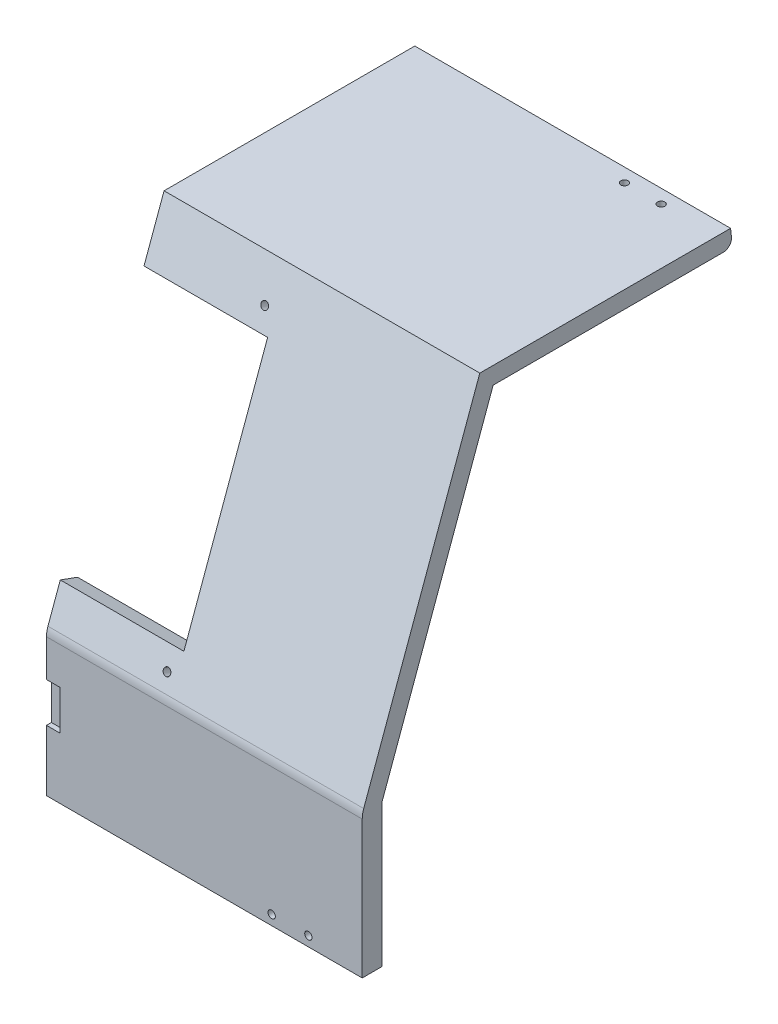
SolidWorks part; units mm, degrees
ref_plane "Front Plane" through (0, 0, 0) normal (0, 0, 1) x (1, 0, 0)
ref_plane "Top Plane" through (0, 0, 0) normal (0, 1, 0) x (1, 0, 0)
ref_plane "Right Plane" through (0, 0, 0) normal (1, 0, 0) x (0, 0, -1)
sketch "Sketch1" plane through (0, 0, 0) normal (0, 0, 1) x (1, 0, 0)
  line L0 (0, 0) -> (170, 0)
  line L1 (170, 0) -> (170, 130)
  line L2 (170, 130) -> (0, 130)
  line L3 (0, 130) -> (0, 0)
  dimension "D1" = 170
  dimension "D2" = 130
extrude "Boss-Extrude1" add sketch "Sketch1" along normal blind 8
sketch "Sketch2" plane through (0, 0, 8) normal (0, 0, 1) x (1, 0, 0)
  line L0 (85, 130) -> (85, 0) construction
  line L1 (170, 130) -> (0, 130) construction
  line L2 (0, 0) -> (170, 0) construction
  line L3 (0, 65) -> (170, 65) construction
  line L4 (0, 130) -> (0, 0) construction
  line L5 (170, 0) -> (170, 130) construction
  line L6 (6.55, 123.35) -> (163.45, 123.35) construction
  line L7 (163.45, 123.35) -> (163.45, 6.65) construction
  line L8 (163.45, 6.65) -> (6.55, 6.65) construction
  line L9 (6.55, 6.65) -> (6.55, 123.35) construction
  line L10 (2.5, 115) -> (167.5, 115)
  line L11 (2.5, 115) -> (2.5, 15)
  line L12 (2.5, 15) -> (167.5, 15)
  line L13 (167.5, 15) -> (167.5, 115)
  circle A0 centre (6.55, 123.35) radius 1.5
  circle A1 centre (163.45, 123.35) radius 1.5
  circle A2 centre (6.55, 6.65) radius 1.5
  circle A3 centre (163.45, 6.65) radius 1.5
  dimension "D3" = 165
  dimension "D1" = 156.9
  dimension "D2" = 116.7
  dimension "D4" = 100
extrude "Cut-Extrude1" cut sketch "Sketch2" against normal blind 21
sketch "Sketch3" plane through (0, 0, 8) normal (0, 0, 1) x (1, 0, 0)
  line L0 (0, 0) -> (170, 0)
  line L1 (170, 0) -> (170, -20)
  line L2 (170, -20) -> (0, -20)
  line L3 (0, -20) -> (0, 0)
extrude "Boss-Extrude2" add sketch "Sketch3" against normal blind 8
sketch "Sketch4" plane through (0, 0, 8) normal (0, 0, 1) x (1, 0, 0)
  line L0 (0, 0) -> (0, -20) construction
  line L1 (0, -10) -> (170, -10) construction
  line L2 (170, -20) -> (170, 130) construction
  line L3 (85, 15) -> (85, -20) construction
  line L4 (2.5, 15) -> (167.5, 15) construction
  line L5 (0, -20) -> (170, -20) construction
  line L6 (52.5, -1.9) -> (52.5, -18.1)
  line L7 (52.5, -1.9) -> (117.5, -1.9)
  line L8 (117.5, -1.9) -> (117.5, -18.1)
  line L9 (117.5, -18.1) -> (52.5, -18.1)
  dimension "D1" = 65
  dimension "D2" = 16.2
extrude "Cut-Extrude2" cut sketch "Sketch4" against normal blind 2
sketch "Sketch5" plane through (0, 0, 6) normal (0, 0, 1) x (1, 0, 0)
  line L0 (52.5, -10) -> (117.5, -10) construction
  line L1 (52.5, -1.9) -> (52.5, -18.1) construction
  line L2 (117.5, -18.1) -> (117.5, -1.9) construction
  line L3 (67.5, -1.9) -> (67.5, -18.1) construction
  line L4 (117.5, -1.9) -> (52.5, -1.9) construction
  line L5 (52.5, -18.1) -> (117.5, -18.1) construction
  line L6 (85, -1.9) -> (85, -18.1) construction
  line L7 (117.5, -1.9) -> (52.5, -1.9) construction
  line L8 (52.5, -18.1) -> (117.5, -18.1) construction
  line L9 (102.5, -1.9) -> (102.5, -18.1) construction
  line L10 (52.5, -1.9) -> (52.5, -18.1) construction
  line L11 (93.75, -1.9) -> (93.75, -18.1) construction
  line L12 (61.5, -4) -> (73.5, -4) construction
  line L13 (73.5, -4) -> (73.5, -16) construction
  line L14 (73.5, -16) -> (61.5, -16) construction
  line L15 (61.5, -16) -> (61.5, -4) construction
  line L16 (96.5, -16) -> (96.5, -4) construction
  line L17 (79, -4) -> (79, -16) construction
  line L18 (79, -16) -> (91, -16) construction
  line L19 (91, -16) -> (91, -4) construction
  line L20 (91, -4) -> (79, -4) construction
  line L21 (108.5, -16) -> (96.5, -16) construction
  line L22 (108.5, -4) -> (108.5, -16) construction
  line L23 (96.5, -4) -> (108.5, -4) construction
  line L24 (61.5, -4) -> (65, -4)
  line L25 (65, -4) -> (65, -16)
  line L26 (65, -16) -> (61.5, -16)
  line L27 (61.5, -16) -> (61.5, -4)
  line L28 (70, -16) -> (73.5, -16)
  line L29 (70, -4) -> (70, -16)
  line L30 (73.5, -4) -> (70, -4)
  line L31 (73.5, -16) -> (73.5, -4)
  line L32 (76.25, -1.9) -> (76.25, -18.1) construction
  line L33 (82.5, -4) -> (82.5, -16)
  line L34 (79, -4) -> (82.5, -4)
  line L35 (79, -16) -> (79, -4)
  line L36 (82.5, -16) -> (79, -16)
  line L37 (87.5, -16) -> (91, -16)
  line L38 (87.5, -4) -> (87.5, -16)
  line L39 (91, -4) -> (87.5, -4)
  line L40 (91, -16) -> (91, -4)
  line L41 (100, -4) -> (100, -16)
  line L42 (96.5, -4) -> (100, -4)
  line L43 (96.5, -16) -> (96.5, -4)
  line L44 (100, -16) -> (96.5, -16)
  line L45 (108.5, -4) -> (105, -4)
  line L46 (108.5, -16) -> (108.5, -4)
  line L47 (105, -16) -> (108.5, -16)
  line L48 (105, -4) -> (105, -16)
  dimension "D1" = 15
  dimension "D2" = 17.5
  dimension "D3" = 17.5
  dimension "D4" = 15
  dimension "D5" = 12
  dimension "D6" = 12
  dimension "D7" = 8.75
  dimension "D8" = 8.75
extrude "Cut-Extrude3" cut sketch "Sketch5" against normal blind 35
sketch "Sketch6" plane through (0, 0, 8) normal (0, 0, 1) x (1, 0, 0)
  line L0 (15.5044, 140) -> (225, 140)
  line L1 (225, 140) -> (225, -35)
  line L2 (225, -35) -> (-10, -35)
  line L3 (-10, -35) -> (-10, 140)
  line L4 (-10, 140) -> (15.5044, 140)
  line L5 (170, 130) -> (0, 130) construction
  line L6 (170, -20) -> (170, 130) construction
  line L7 (0, -20) -> (170, -20) construction
  line L8 (0, 130) -> (170, 130)
  line L9 (170, 130) -> (170, -20)
  line L10 (170, -20) -> (0, -20)
  line L11 (0, -20) -> (0, 130)
  dimension "D1" = 10
  dimension "D2" = 10
  dimension "D3" = 55
  dimension "D4" = 15
extrude "Boss-Extrude3" add sketch "Sketch6" against normal blind 8
sketch "Sketch7" plane through (0, 0, 8) normal (0, 0, 1) x (1, 0, 0)
  line L0 (-10, 140) -> (-17, 140)
  line L1 (-17, 140) -> (-17, -42)
  line L2 (-17, -42) -> (232, -42)
  line L3 (232, -42) -> (232, 140)
  line L4 (232, 140) -> (225, 140)
  line L5 (225, 140) -> (225, -35)
  line L6 (225, -35) -> (-10, -35)
  line L7 (-10, -35) -> (-10, 140)
  dimension "D1" = 7
  dimension "D2" = 7
  dimension "D3" = 7
extrude "Boss-Extrude4" add sketch "Sketch7" against normal blind 138
sketch "Sketch8" plane through (0, -42, 0) normal (0, -1, 0) x (1, 0, 0)
  line L0 (-17, 8) -> (-17, -130)
  line L1 (-17, -130) -> (232, -130)
  line L2 (232, -130) -> (232, 8)
  line L3 (232, 8) -> (-17, 8)
extrude "Boss-Extrude5" add sketch "Sketch8" along normal blind 1
sketch "Sketch9" plane through (232, 0, 0) normal (1, 0, 0) x (0, 0, -1)
  line L0 (75, 140) -> (75, -48) construction
  line L1 (130, 140) -> (-8, 140) construction
  line L3 (-8, -43) -> (-8, 140) construction
  line L4 (-8, 35) -> (130, 35) construction
  line L5 (130, -43) -> (130, 140) construction
  line L6 (38.6, 71.625) -> (111.4, 71.625)
  line L7 (111.4, 71.625) -> (111.4, -1.625)
  line L8 (111.4, -1.625) -> (38.6, -1.625)
  line L9 (38.6, -1.625) -> (38.6, 71.625)
  dimension "D1" = 105
  dimension "D2" = 72.8
  dimension "D3" = 73.25
  dimension "D4" = 75
extrude "Cut-Extrude4" cut sketch "Sketch9" against normal blind 19
sketch "Sketch10" plane through (232, 0, 0) normal (1, 0, 0) x (0, 0, -1)
  line L0 (75, 71.625) -> (75, -1.625) construction
  line L1 (38.6, 35) -> (111.4, 35) construction
  line L2 (111.4, -1.625) -> (111.4, 71.625) construction
  line L3 (38.6, 71.625) -> (38.6, -1.625) construction
  line L4 (111.4, 71.625) -> (38.6, 71.625) construction
  line L5 (38.6, -1.625) -> (111.4, -1.625) construction
  line L6 (36, 74) -> (114, 74) construction
  line L7 (36, 74) -> (36, -4) construction
  line L8 (36, -4) -> (114, -4) construction
  line L9 (114, -4) -> (114, 74) construction
  line L10 (36, 44) -> (36, -4)
  line L11 (36, -4) -> (114, -4)
  line L12 (114, -4) -> (114, 44)
  line L13 (114, 44) -> (119, 44)
  line L14 (119, 44) -> (119, -9)
  line L15 (119, -9) -> (31, -9)
  line L16 (31, -9) -> (31, 44)
  line L17 (31, 44) -> (36, 44)
  dimension "D1" = 78
  dimension "D2" = 78
  dimension "D3" = 5
  dimension "D4" = 5
  dimension "D5" = 5
  dimension "D6" = 30
  dimension "D7" = 30
extrude "Boss-Extrude6" add sketch "Sketch10" along normal blind 5
sketch "Sketch11" plane through (237, 0, 0) normal (1, 0, 0) x (0, 0, -1)
  line L0 (33.5, 44) -> (33.5, -9) construction
  line L1 (36, 44) -> (31, 44) construction
  line L2 (31, -9) -> (119, -9) construction
  line L3 (116.5, 44) -> (116.5, -9) construction
  line L4 (119, 44) -> (114, 44) construction
  circle A0 centre (33.5, 17.5) radius 1.5
  circle A1 centre (116.5, 17.5) radius 1.5
extrude "Cut-Extrude5" cut sketch "Sketch11" against normal blind 56
sketch "Sketch12" plane through (0, -35, 0) normal (0, 1, 0) x (1, 0, 0)
  line L0 (107.5, 130) -> (107.5, 0) construction
  line L1 (225, 130) -> (-10, 130) construction
  line L2 (-10, 0) -> (225, 0) construction
  line L3 (107.5, 65) -> (225, 65) construction
  line L4 (153.75, 107) -> (153.75, 83) construction
  line L5 (225, 130) -> (225, 0) construction
  line L6 (166.25, 65) -> (166.25, 0) construction
  line L7 (225, 0) -> (-10, 0) construction
  line L8 (166.25, 65) -> (166.25, 130) construction
  line L9 (153.75, 107) -> (178.75, 107) construction
  line L10 (153.75, 83) -> (178.75, 83) construction
  line L11 (178.75, 83) -> (178.75, 107) construction
  line L12 (155.75, 107) -> (155.75, 83) construction
  line L13 (176.75, 107) -> (176.75, 83) construction
  line L14 (153.75, 97.5) -> (178.75, 97.5) construction
  line L15 (153.75, 85) -> (178.75, 85) construction
  line L16 (187.25, 130) -> (187.25, 65) construction
  line L17 (145.25, 130) -> (145.25, 65) construction
  circle A0 centre (166.25, 32.5) radius 9
  circle A1 centre (166.25, 97.5) radius 6.5
  circle A2 centre (155.75, 97.5) radius 1
  circle A3 centre (155.75, 85) radius 1
  circle A4 centre (176.75, 85) radius 1
  circle A5 centre (176.75, 97.5) radius 1
  circle A6 centre (145.25, 97.5) radius 2.75
  circle A7 centre (187.25, 97.5) radius 2.75
  dimension "D1" = 18
  dimension "D2" = 25
  dimension "D4" = 13
  dimension "D7" = 21
  dimension "D8" = 24
  dimension "D3" = 9.5
  dimension "D5" = 2
  dimension "D6" = 12.5
extrude "Cut-Extrude6" cut sketch "Sketch12" against normal blind 115
sketch "Sketch13" plane through (0, -43, 0) normal (0, -1, 0) x (1, 0, 0)
  line L0 (107.5, 8) -> (107.5, -130) construction
  line L1 (232, 8) -> (-17, 8) construction
  line L2 (-17, -130) -> (232, -130) construction
  line L3 (107.5, -61) -> (232, -61) construction
  line L4 (232, -130) -> (232, 8) construction
  line L5 (166.25, -97.5) -> (166.25, -61) construction
  line L6 (136.9548, -61) -> (136.9548, -130) construction
  line L7 (195.5452, -61) -> (195.5452, -130) construction
  line L8 (136.9548, -78.4497) -> (195.5452, -78.4497) construction
  line L9 (136.9548, -108.5255) -> (195.5452, -108.5255) construction
  line L10 (136.9548, -78.4497) -> (195.5452, -78.4497)
  line L11 (195.5452, -78.4497) -> (195.5452, -108.5255)
  line L12 (195.5452, -108.5255) -> (136.9548, -108.5255)
  line L13 (136.9548, -108.5255) -> (136.9548, -78.4497)
  dimension "D1" = 124.5
  dimension "D2" = 124.5
extrude "Cut-Extrude7" cut sketch "Sketch13" against normal blind 3
fillet "Fillet1" radius 2 4 edges at (136.9548, -40, -93.4876) (166.25, -40, -108.5255) (195.5452, -40, -93.4876) (166.25, -40, -78.4497)
sketch "Sketch15" plane through (0, 140, 0) normal (0, 1, 0) x (1, 0, 0)
  line L0 (-17, -4) -> (232, -4) construction
  line L1 (-17, 130) -> (-17, -8) construction
  line L2 (232, 130) -> (232, -8) construction
  line L3 (232, -8) -> (-17, -8) construction
  circle A0 centre (5, -4) radius 1.5
  circle A1 centre (20, -4) radius 1.5
  circle A2 centre (217, -4) radius 1.5
  circle A3 centre (202, -4) radius 1.5
  dimension "D2" = 15
  dimension "D1" = 4
  dimension "D3" = 15
  dimension "D4" = 15
  dimension "D5" = 15
extrude "Cut-Extrude8" cut sketch "Sketch15" against normal blind 10
ref_plane "Plane3" through (0, 1.7547, 4.8209) normal (0, 0.342, 0.9397) x (1, 0, 0)
sketch "Sketch18" plane through (232, 0, 0) normal (1, 0, 0) x (0, 0, -1)
  line L0 (45.4963, 140) -> (-8, 140)
  line L1 (130, 140) -> (-8, 140) construction
  line L2 (42.0188, 130.4456) -> (-51.6606, -126.9362) construction
  line L3 (-8, 140) -> (-8, 15)
  line L4 (-8, 15) -> (0, 15)
  line L5 (0, 15) -> (-8, 15) construction
  line L6 (0, 15) -> (45.4963, 140)
extrude "Cut-Extrude10" cut sketch "Sketch18" against normal blind 261
sketch "Sketch19" plane through (0, 0, 8) normal (0, 0, 1) x (1, 0, 0)
  circle A0 centre (6.55, 6.65) radius 1.5
  circle A1 centre (163.45, 6.65) radius 1.5
extrude "Boss-Extrude7" add sketch "Sketch19" against normal up to surface (8 mm away) up to face at (63.25, -10, 0)
ref_plane "Plane4" through (107.5, 0, 0) normal (1, 0, 0) x (0, 0, -1)
sketch "Sketch21" plane through (107.5, 0, 0) normal (1, 0, 0) x (0, 0, -1)
  line L0 (45.4963, 140) -> (0, 15)
  line L1 (42.0188, 130.4456) -> (-51.6606, -126.9362) construction
  line L2 (130, 140) -> (45.4963, 140) construction
  line L3 (0, 15) -> (-8, 15)
  line L4 (-8, 15) -> (37.4963, 140)
  line L5 (37.4963, 140) -> (45.4963, 140)
  dimension "D1" = 8
  dimension "D2" = 8
extrude "Boss-Extrude12" add sketch "Sketch21" along normal up to surface (124.5 mm away) and the other way up to surface (124.5 mm away) up to face at (232, 37.3333, -48.2494) other way up to face at (-17, 37.3333, -48.2494)
sketch "Sketch22" plane through (0, 4.3258, 11.8851) normal (0, 0.342, 0.9397) x (1, 0, 0)
  line L0 (177, 144.3814) -> (177, 11.3592) construction
  line L1 (232, 144.3814) -> (-17, 144.3814) construction
  line L2 (-17, 11.3592) -> (232, 11.3592) construction
  line L3 (232, 144.3814) -> (232, 11.3592) construction
  line L4 (177, 77.8703) -> (-17, 77.8703) construction
  line L5 (-17, 144.3814) -> (-17, 11.3592) construction
  line L6 (80, 77.8703) -> (80, 11.3592) construction
  line L7 (80, 77.8703) -> (80, 144.3814) construction
  line L8 (1.55, 136.2203) -> (158.45, 136.2203) construction
  line L9 (158.45, 136.2203) -> (158.45, 19.5203) construction
  line L10 (158.45, 19.5203) -> (1.55, 19.5203) construction
  line L11 (1.55, 19.5203) -> (1.55, 136.2203) construction
  line L12 (-2.5, 127.8703) -> (-2.5, 27.8703)
  line L13 (-2.5, 27.8703) -> (162.5, 27.8703)
  line L14 (162.5, 27.8703) -> (162.5, 127.8703)
  line L15 (162.5, 127.8703) -> (-2.5, 127.8703)
  circle A0 centre (1.55, 136.2203) radius 1.5
  circle A1 centre (158.45, 136.2203) radius 1.5
  circle A2 centre (1.55, 19.5203) radius 1.5
  circle A3 centre (158.45, 19.5203) radius 1.5
  dimension "D5" = 100
  dimension "D1" = 55
  dimension "D2" = 133.0222
  dimension "D3" = 116.7
  dimension "D4" = 156.9
  dimension "D6" = 165
extrude "Cut-Extrude11" cut sketch "Sketch22" against normal blind 18
fillet "Fillet2" radius 10 1 edges at (107.5, 15, 8)
sketch "Sketch24" plane through (-10, 0, 0) normal (1, 0, 0) x (0, 0, -1)
  line L0 (130, 48.5) -> (12.193, 48.5) construction
  line L1 (130, -43) -> (130, 140) construction
  line L2 (45.4963, 140) -> (0, 15) construction
  line L3 (108, 83.5) -> (108, 13.5) construction
  line L4 (108, 83.5) -> (130, 83.5) construction
  line L5 (108, 13.5) -> (130, 13.5) construction
  line L6 (130, 13.5) -> (130, 83.5) construction
  line L7 (108, 28.5) -> (130, 28.5) construction
  line L8 (108, 68.5) -> (130, 68.5) construction
  line L9 (113.5, 13.5) -> (113.5, 83.5) construction
  line L10 (119.5, 83.5) -> (119.5, 13.5) construction
  line L11 (130, 84.5) -> (127, 84.5)
  line L12 (127, 84.5) -> (127, 12.5)
  line L13 (127, 12.5) -> (130, 12.5)
  line L14 (130, 12.5) -> (130, 84.5)
  circle A0 centre (113.5, 48.5) radius 2
  circle A1 centre (119.5, 68.5) radius 2
  circle A2 centre (119.5, 28.5) radius 2
  dimension "D7" = 72
  dimension "D1" = 70
  dimension "D2" = 22
  dimension "D3" = 15
  dimension "D4" = 20
  dimension "D5" = 5.5
  dimension "D6" = 11.5
extrude "Cut-Extrude15" cut sketch "Sketch24" against normal blind 42
sketch "Sketch25" plane through (232, 0, 0) normal (1, 0, 0) x (0, 0, -1)
  line L0 (45.4963, 140) -> (130, 140)
  line L1 (130, 140) -> (130, -43)
  line L2 (130, -43) -> (0, -43)
  line L3 (130, -43) -> (-8, -43) construction
  line L4 (0, -43) -> (0, 15)
  line L5 (0, 15) -> (45.4963, 140)
extrude "Cut-Extrude16" cut sketch "Sketch25" against normal up to surface (242 mm away) and the other way blind 140 up to face at (-10, 50.5, -113.5)
sketch "Sketch27" plane through (0, 140, 0) normal (0, 1, 0) x (1, 0, 0)
  line L0 (232, 37.4963) -> (232, 142.4963)
  line L1 (232, 142.4963) -> (-17, 142.4963)
  line L2 (-17, 142.4963) -> (-17, 37.4963)
  line L3 (-17, 37.4963) -> (232, 37.4963)
extrude "Boss-Extrude13" add sketch "Sketch27" along normal blind 7
sketch "Sketch28" plane through (232, 0, 0) normal (1, 0, 0) x (0, 0, -1)
  line L0 (37.4963, 140) -> (40.0441, 147)
  line L1 (37.4963, 147) -> (142.4963, 147) construction
  line L2 (0, 15) -> (45.4963, 140) construction
  line L3 (40.0441, 147) -> (37.4963, 147)
  line L4 (37.4963, 147) -> (37.4963, 140)
extrude "Cut-Extrude17" cut sketch "Sketch28" against normal up to surface (249 mm away) up to face at (-17, 46.5, -113.5)
fillet "Fillet6" radius 3 1 edges at (107.5, 140, -142.4963)
fillet "Fillet7" radius 3 3 edges at (-17, 145, -142.4963) (-17, 140.8787, -141.6176) (-17, 140, -134.7481)
sketch "Sketch29" plane through (232, 0, 0) normal (1, 0, 0) x (0, 0, -1)
  line L0 (-8, -43) -> (0, -43)
  line L1 (0, -43) -> (0, 15)
  line L2 (0, 15) -> (45.4963, 140)
  line L3 (45.4963, 140) -> (139.4963, 140)
  line L4 (142.8768, 143.3805) -> (142.4963, 147)
  line L5 (142.4963, 147) -> (40.0441, 147)
  line L6 (40.0441, 147) -> (-7.3969, 16.6569)
  line L7 (-8, 13.2367) -> (-8, -43)
  arc A0 (139.4963, 140) -> (142.8768, 143.3805) centre (139.4963, 143.3805) ccw
  arc A1 (-7.3969, 16.6569) -> (-8, 13.2367) centre (2, 13.2367) ccw
extrude "Boss-Extrude14" add sketch "Sketch29" along normal blind 9
sketch "Sketch30" plane through (0, 147, 0) normal (0, 1, 0) x (1, 0, 0)
  line L0 (241, 140.8768) -> (241, 132.8768) construction
  line L1 (203.25, 142.4963) -> (203.25, 129.9214) construction
  line L2 (241, 136.8768) -> (104.3928, 136.8768) construction
  line L3 (233.25, 142.4963) -> (233.25, 132.8768) construction
  line L4 (218.25, 142.4963) -> (218.25, 129.9214) construction
  line L5 (232, 142.4963) -> (-14, 142.4963) construction
  circle A0 centre (218.25, 136.8768) radius 1.5
  circle A1 centre (203.25, 136.8768) radius 1.5
  dimension "D1" = 2
  dimension "D2" = 8
  dimension "D3" = 7.75
  dimension "D4" = 15
  dimension "D5" = 1.6195
  dimension "D6" = 15
extrude "Cut-Extrude18" cut sketch "Sketch30" against normal blind 10
sketch "Sketch31" plane through (0, 0, 8) normal (0, 0, 1) x (1, 0, 0)
  line L0 (241, -43) -> (241, -35) construction
  line L1 (241, 13.2367) -> (241, -43) construction
  line L2 (241, -39) -> (190.9905, -39) construction
  line L3 (234, -35) -> (234, -43) construction
  line L4 (241, -43) -> (-17, -43) construction
  line L5 (219, -35) -> (219, -43) construction
  line L6 (204, -35) -> (204, -43) construction
  circle A0 centre (219, -39) radius 1.5
  circle A1 centre (204, -39) radius 1.5
  dimension "D1" = 7
  dimension "D2" = 15
  dimension "D3" = 15
extrude "Cut-Extrude19" cut sketch "Sketch31" against normal blind 49
sketch "Sketch32" plane through (-17, 0, 0) normal (-1, 0, 0) x (0, 0, 1)
  line L0 (-110, -6.7633) -> (-12, -6.7633) construction
  line L1 (-110, -6.7633) -> (-12, -6.7633) construction
  line L2 (-110, 0.7367) -> (-12, 0.7367)
  line L3 (-110, -14.2633) -> (-12, -14.2633)
  line L4 (-130, 12.5) -> (-130, -43) construction
  line L5 (8, 13.2367) -> (8, -43) construction
  line L6 (-110, 112) -> (-48.5887, 112) construction
  line L7 (-110, 112) -> (-48.5887, 112) construction
  line L8 (-110, 119.5) -> (-48.5887, 119.5)
  line L9 (-110, 104.5) -> (-48.5887, 104.5)
  line L10 (-130, 143) -> (-130, 84.5) construction
  line L11 (-40.0441, 147) -> (7.3969, 16.6569) construction
  line L12 (-139.4963, 147) -> (-40.0441, 147) construction
  arc A0 (-110, 0.7367) -> (-110, -14.2633) centre (-110, -6.7633) ccw
  arc A1 (-12, -14.2633) -> (-12, 0.7367) centre (-12, -6.7633) ccw
  arc A2 (8, 13.2367) -> (7.3969, 16.6569) centre (-2, 13.2367) ccw construction
  arc A3 (-110, 119.5) -> (-110, 104.5) centre (-110, 112) ccw
  arc A4 (-48.5887, 104.5) -> (-48.5887, 119.5) centre (-48.5887, 112) ccw
  point P3 (-61, -6.7633)
  point P18 (-79.2943, 112)
  dimension "D1" = 20
  dimension "D2" = 20
  dimension "D3" = 15
  dimension "D4" = 20
  dimension "D5" = 20
  dimension "D6" = 20
  dimension "D7" = 35
  dimension "D8" = 15
extrude "Cut-Extrude20" cut sketch "Sketch32" against normal blind 49
sketch "Sketch34" plane through (0, 0, 8) normal (0, 0, 1) x (1, 0, 0)
  line L0 (112, -43) -> (112, 147) construction
  line L1 (241, -43) -> (-17, -43) construction
  line L2 (-17, 147) -> (241, 147) construction
  line L3 (112, -43) -> (112, 147)
  line L4 (112, 147) -> (-17, 147)
  line L5 (-17, 147) -> (-17, -43)
  line L6 (-17, -43) -> (112, -43)
extrude "Cut-Extrude21" cut sketch "Sketch34" against normal blind 222
